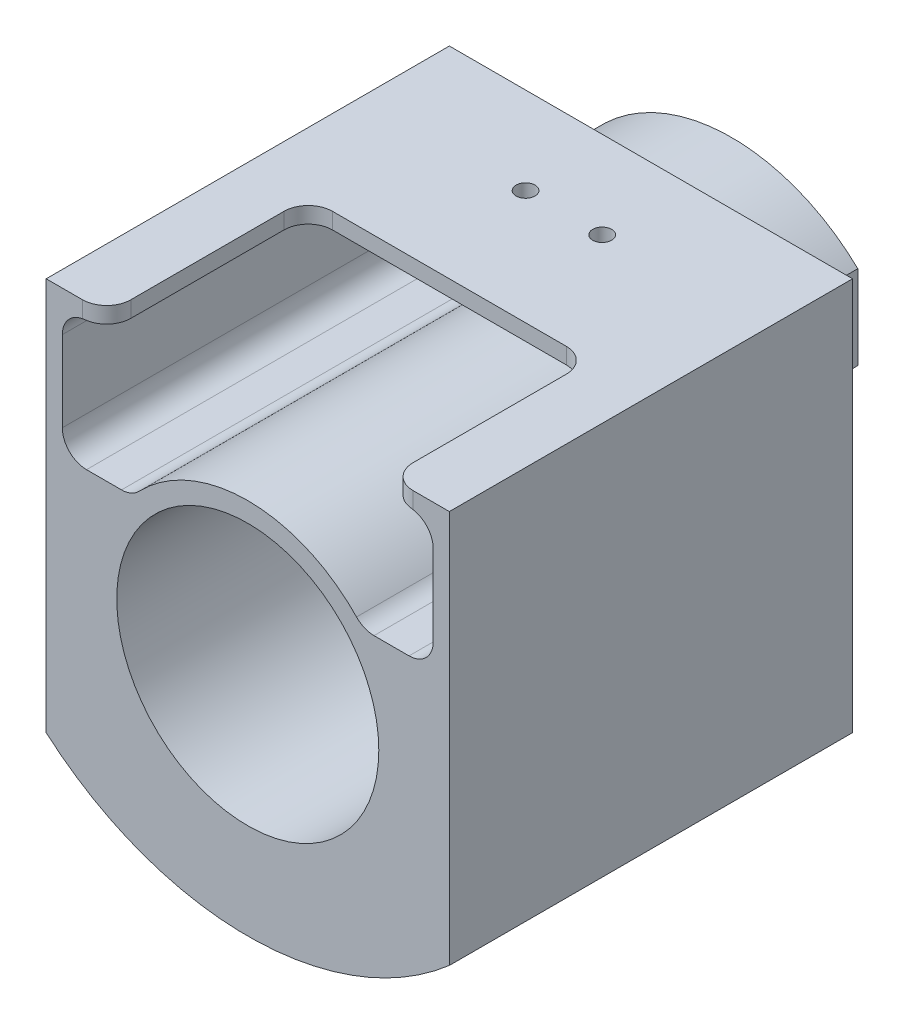
SolidWorks part; units mm, degrees
ref_plane "Front Plane" through (0, 0, 0) normal (0, 0, 1) x (1, 0, 0)
ref_plane "Top Plane" through (0, 0, 0) normal (0, 1, 0) x (1, 0, 0)
ref_plane "Right Plane" through (0, 0, 0) normal (1, 0, 0) x (0, 0, -1)
sketch "Sketch1" plane through (0, 0, 0) normal (0, 0, 1) x (1, 0, 0)
  line L1 (0, 0) -> (0, -38.1) construction
  line L2 (-25, 0) -> (-25, -28.7508)
  line L3 (25, 0) -> (25, -28.7508)
  line L4 (-25, 0) -> (-25, 20)
  line L5 (-25, 20) -> (25, 20)
  line L6 (25, 20) -> (25, 0)
  arc A0 (-25, -28.7508) -> (25, -28.7508) centre (0, 0) ccw
  dimension "D1" = 76.2
  dimension "D2" = 50
  dimension "D3" = 20
extrude "Boss-Extrude2" add sketch "Sketch1" along normal blind 50
sketch "Sketch2" plane through (0, 0, 50) normal (0, 0, 1) x (1, 0, 0)
  line L6 (0, 6.25) -> (0, -26.25) construction
  circle A0 centre (0, -10) radius 16.25
  dimension "D2" = 32.5
  dimension "D1" = 10
extrude "Cut-Extrude1" cut sketch "Sketch2" against normal through all both
sketch "Sketch4" plane through (0, 0, 50) normal (0, 0, 1) x (1, 0, 0)
  line L0 (-23, 18) -> (23, 18)
  line L3 (0, 20) -> (0, 6.25) construction
  line L4 (25, 20) -> (-25, 20) construction
  line L5 (23, 2) -> (14.3178, 2)
  line L6 (-23, 18) -> (-23, 2)
  line L7 (-23, 2) -> (-14.3178, 2)
  line L8 (-25, 20) -> (-25, -28.7508) construction
  line L9 (23, 18) -> (23, 2)
  circle A2 centre (0, -10) radius 16.25 construction
  arc A3 (14.3178, 2) -> (-14.3178, 2) centre (0, -10) ccw
  point P2 (0, 13.125)
  point P14 (0, 18)
  dimension "D1" = 37.3631
  dimension "D2" = 2
  dimension "D3" = 2
  dimension "D4" = 16
extrude "Cut-Extrude3" cut sketch "Sketch4" against normal through all
fillet "Fillet1" radius 3 6 edges at (23, 18, 25) (23, 2, 25) (14.3178, 2, 25) (-14.3178, 2, 25) (-23, 2, 25) (-23, 18, 25)
sketch "Sketch5" plane through (0, 20, 0) normal (0, 1, 0) x (1, 0, 0)
  line L0 (25, -50) -> (-25, -50) construction
  line L1 (-17.5, -50) -> (17.5, -50)
  line L2 (-17.5, -50) -> (-17.5, -25)
  line L3 (-17.5, -25) -> (17.5, -25)
  line L4 (17.5, -50) -> (17.5, -25)
  line L5 (0, 0) -> (0, -50) construction
  dimension "D1" = 35
  dimension "D2" = 25
extrude "Cut-Extrude4" cut sketch "Sketch5" against normal blind 10
fillet "Fillet2" radius 3 4 edges at (17.5, 19, 50) (17.5, 19, 25) (-17.5, 19, 25) (-17.5, 19, 50)
ref_plane "Plane1" through (0, 0, 14) normal (0, 0, 1) x (1, 0, 0)
sketch "Sketch6" plane through (0, 0, 14) normal (0, 0, 1) x (1, 0, 0)
  line L0 (0, -10) -> (0, 3) construction
  line L1 (0, -10) -> (4.9749, 2.0104) construction
  circle A1 centre (0, -10) radius 16.25 construction
  circle A3 centre (0, -10) radius 9.5
  circle A8 centre (0, -10) radius 16.25
  circle A9 centre (0, -10) radius 13 construction
  circle A10 centre (4.9749, 2.0104) radius 1.65
  circle A11 centre (12.0104, -14.9749) radius 1.65
  circle A12 centre (-4.9749, -22.0104) radius 1.65
  circle A13 centre (-12.0104, -5.0251) radius 1.65
  point P5 (0, 0)
  dimension "D1" = 19
  dimension "D2" = 3.5
  dimension "D3" = 3.3
  dimension "D4" = 22.5
  dimension "D5" = 4
extrude "Boss-Extrude3" add sketch "Sketch6" against normal blind 5
sketch "Sketch7" plane through (0, 0, 0) normal (1, 0, 0) x (0, 0, -1)
  circle A0 centre (-40, -32) radius 2.25
  circle A1 centre (-10, -32) radius 2.25
  dimension "D3" = 4.5
  dimension "D1" = 32
  dimension "D2" = 10
  dimension "D4" = 30
extrude "Cut-Extrude5" cut sketch "Sketch7" against normal through all both and the other way through all
sketch "Sketch8" plane through (0, 20, 0) normal (0, 1, 0) x (1, 0, 0)
  line L0 (0, 0) -> (0, -25) construction
  line L1 (25, 0) -> (-25, 0) construction
  line L2 (14.5, -25) -> (-14.5, -25) construction
  circle A0 centre (-4.75, -10.8) radius 1.175
  circle A1 centre (4.75, -10.8) radius 1.175
  dimension "D1" = 2.35
  dimension "D2" = 9.5
  dimension "D3" = 10.8
extrude "Cut-Extrude6" cut sketch "Sketch8" against normal up to next contours A0 | A1
sketch "Sketch9" plane through (0, 0, 50) normal (0, 0, 1) x (1, 0, 0)
  line L0 (0, -28.5) -> (0, -5) construction
  line L1 (0, -10) -> (0, -28.5) construction
  line L2 (-15.6553, 2) -> (-15.6553, 11.4123)
  line L3 (15.6553, 2) -> (15.6553, 11.4123)
  line L4 (0, 8.6815) -> (0, 17.6815) construction
  line L5 (-14.6553, 2.1716) -> (-14.6553, 10.5325)
  line L6 (14.6553, 2.1716) -> (14.6553, 10.5325)
  line L7 (-15.6553, 2) -> (-15.6553, 1)
  line L8 (15.6553, 2) -> (15.6553, 1)
  line L9 (14.6553, 2) -> (14.6553, 10.9784) construction
  line L10 (-14.6553, 2) -> (-14.6553, 10.9784) construction
  arc A0 (13.4892, 2.9245) -> (-13.4892, 2.9245) centre (0, -10) ccw construction
  arc A1 (13.4892, 2.9245) -> (-13.4892, 2.9245) centre (0, -10) ccw
  arc A3 (-15.6553, 11.4123) -> (15.6553, 11.4123) centre (0, -5) cw
  arc A4 (13.4892, 2.9245) -> (15.6553, 2) centre (15.6553, 5) ccw construction
  arc A5 (-15.6553, 2) -> (-13.4892, 2.9245) centre (-15.6553, 5) ccw construction
  arc A6 (13.4892, 2.9245) -> (15.6553, 2) centre (15.6553, 5) ccw
  arc A7 (-15.6553, 2) -> (-13.4892, 2.9245) centre (-15.6553, 5) ccw
  arc A8 (12.7671, 2.2327) -> (15.6553, 1) centre (15.6553, 5) ccw
  arc A9 (12.7671, 2.2327) -> (-12.7671, 2.2327) centre (0, -10) ccw
  arc A10 (-15.6553, 1) -> (-12.7671, 2.2327) centre (-15.6553, 5) ccw
  arc A11 (-14.3156, 11.2835) -> (14.3156, 11.2835) centre (0, -5) cw
  arc A12 (-14.6553, 10.9784) -> (14.6553, 10.9784) centre (0, -5) cw construction
  arc A13 (14.6553, 10.5325) -> (14.3156, 11.2835) centre (13.6553, 10.5325) ccw
  arc A14 (-14.6553, 10.5325) -> (-14.3156, 11.2835) centre (-13.6553, 10.5325) cw
  dimension "D1" = 9
  dimension "D2" = 1
  dimension "D4" = 1
  dimension "Ring Gear Outer Dia to Center" = 23.5
  dimension "Pinion to Ring Gear Outer Diameter" = 18.5
  dimension "D3" = 1
extrude "Boss-Extrude4" add sketch "Sketch9" along normal blind 8 and the other way blind 10 from surface contours L5 A11 L6 L2 L3 A3 A6 | L7 A10 A9 A8 L8 L2 L3 A6 region at (-15.0935, 1.7255, 50) region at (-15.3051, 6.7061, 50) starting at face at (0, 7.9303, 0)
fillet "Fillet5" radius 0.25 8 edges at (14.0281, 2.4797, -10) (-14.0281, 2.4797, -10) (14.6553, 6.352, -10) (14.5664, 10.9446, -10) (-14.6553, 6.352, -10) (-14.5664, 10.9446, -10) (0, 8.6815, -10) (0, 16.6815, -10)
fillet "Fillet6" radius 0.25 5 edges at (14.6553, 6.352, 8) (14.5664, 10.9446, 8) (-14.6553, 6.352, 8) (-14.5664, 10.9446, 8) (0, 16.6815, 8)
